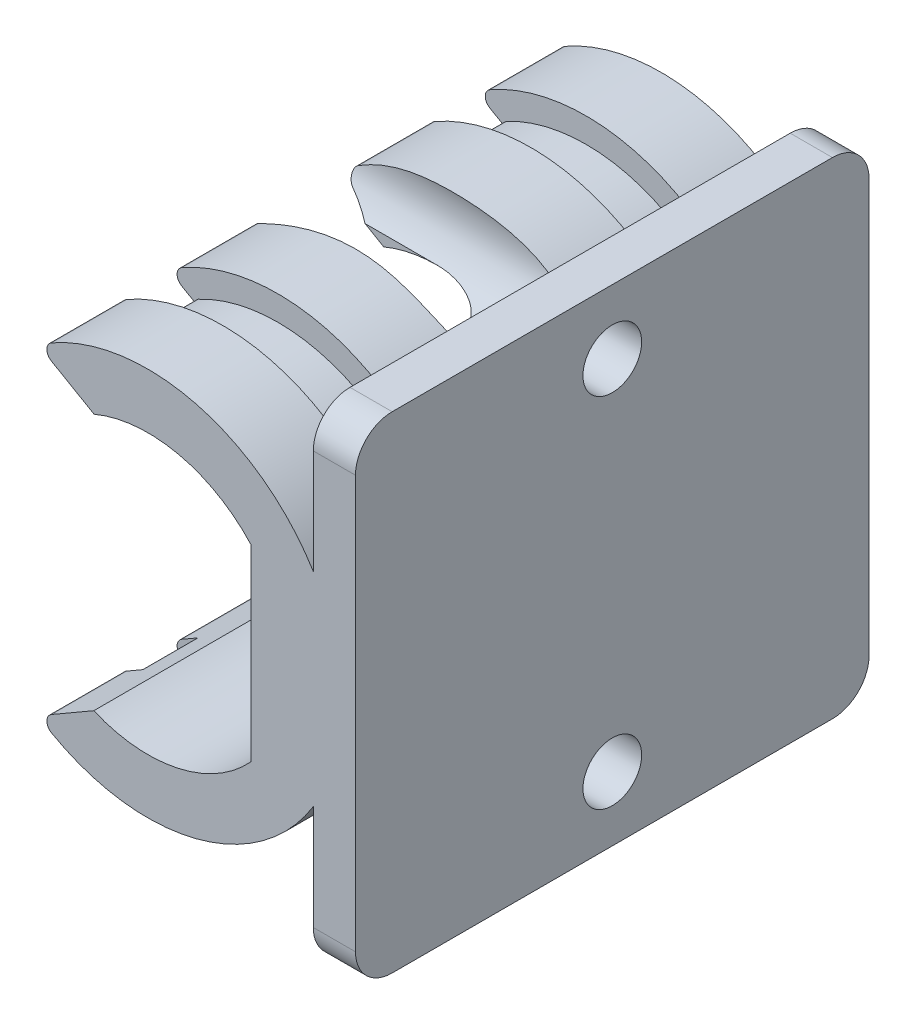
SolidWorks part; units mm, degrees
ref_plane "Alzado" through (0, 0, 0) normal (0, 0, 1) x (1, 0, 0)
ref_plane "Planta" through (0, 0, 0) normal (0, 1, 0) x (1, 0, 0)
ref_plane "Vista lateral" through (0, 0, 0) normal (1, 0, 0) x (0, 0, -1)
sketch "Croquis1" plane through (0, 0, 0) normal (0, 0, 1) x (1, 0, 0)
  line L0 (-9.8945, -9.6573) -> (-6.8675, -7.9093)
  line L1 (-9.8945, 7.8551) -> (-6.8511, 6.0976)
  arc A0 (-6.8675, -7.9093) -> (-6.8511, 6.0976) centre (-3.9083, -0.9093) ccw
  arc A1 (-9.8945, -9.6573) -> (-9.8945, 7.8551) centre (-3.9265, -0.9011) ccw
  point P0 (-6.8675, -7.9093)
  point P1 (-6.8675, 6.0907)
  point P2 (1.6915, 4.2287)
  point P3 (-1.2035, 9.3397)
  point P4 (6.6605, -1.3538)
  point P5 (-9.8945, -9.6573)
extrude "Saliente-Extruir1" add sketch "Croquis1" along normal blind 14.6 and the other way blind 14.6
sketch "Croquis2" plane through (0, 0, 14.6) normal (0, 0, 1) x (1, 0, 0)
  line L1 (1.6917, 4.2285) -> (1.6917, -6.0471)
  arc A0 (-6.8675, -7.9093) -> (-6.8511, 6.0976) centre (-3.9083, -0.9093) ccw construction
  arc A1 (1.6917, -6.0471) -> (1.6917, 4.2285) centre (-3.9083, -0.9093) ccw
  dimension "D1" = 5.6
extrude "Saliente-Extruir2" add sketch "Croquis2" against normal blind 2.6
mirror "Simetría1" about plane through (0, 0, 0) normal (0, 0, 1) of "Saliente-Extruir2"
sketch "Croquis3" plane through (0, 0, 0) normal (0, 0, 1) x (1, 0, 0)
  line L0 (1.6917, -0.9093) -> (20.3236, -0.9093) construction
  line L1 (1.6917, 4.2285) -> (1.6917, -6.0471) construction
  line L3 (5.1, 23.0597) -> (7.4, 23.0597)
  line L4 (5.1, 23.0597) -> (5.1, -24.8783)
  line L5 (5.1, -24.8783) -> (7.4, -24.8783)
  line L6 (7.4, 23.0597) -> (7.4, -24.8783)
  line L7 (5.1, 23.0597) -> (7.4, -24.8783) construction
  line L8 (5.1, -24.8783) -> (7.4, 23.0597) construction
  point P4 (6.25, -0.9093)
  dimension "D1" = 2.3
  dimension "D2" = 5.1
extrude "Saliente-Extruir3" add sketch "Croquis3" along normal up to surface (14.6 mm away) and the other way up to surface (14.6 mm away) up to face at (-2.1614, -0.9063, 14.6) other way up to face at (-2.1614, -0.9063, -14.6)
sketch "Croquis6" plane through (7.4, 0, 0) normal (1, 0, 0) x (0, 0, -1)
  line L0 (0, 23.0597) -> (0, -24.8783) construction
  line L1 (-14.6, 23.0597) -> (14.6, 23.0597) construction
  line L2 (-14.6, -24.8783) -> (14.6, -24.8783) construction
  line L3 (14.6, 4.2285) -> (14.6, -6.0471) construction
  line L4 (14.6, 4.2285) -> (14.6, -6.0471) construction
  line L5 (14.6, -0.9093) -> (-26.9521, -0.9093) construction
  circle A0 centre (0, 8.8407) radius 1.6
  circle A1 centre (0, -10.6593) radius 1.6
  dimension "D1" = 3.2
  dimension "D2" = 9.75
extrude "Cortar-Extruir1" cut sketch "Croquis6" against normal blind 20
sketch "Croquis7" plane through (5.1, 0, 0) normal (-1, 0, 0) x (0, 0, 1)
  circle A0 centre (0, -10.6593) radius 1.6 construction
  circle A1 centre (0, -10.6593) radius 1.6 construction
  circle A2 centre (0, -10.6593) radius 2.8
  circle A3 centre (0, 8.8407) radius 1.6 construction
  circle A4 centre (0, 8.8407) radius 1.6 construction
  circle A5 centre (0, 8.8407) radius 2.8
  dimension "D1" = 5.6
extrude "Cortar-Extruir2" cut sketch "Croquis7" along normal blind 20 contours A2
sketch "Croquis8" plane through (5.1, 0, 0) normal (-1, 0, 0) x (0, 0, 1)
  circle A0 centre (0, 8.8407) radius 1.6 construction
  circle A1 centre (0, 8.8407) radius 1.6 construction
  circle A2 centre (0, 8.8407) radius 2.8
  dimension "D1" = 5.6
extrude "Cortar-Extruir3" cut sketch "Croquis8" along normal blind 33
sketch "Croquis9" plane through (7.4, 0, 0) normal (1, 0, 0) x (0, 0, -1)
  line L0 (-12, 4.2285) -> (-12, -6.0471) construction
  line L2 (-14.6068, -0.9093) -> (14.6068, -0.9093) construction
  line L3 (-12, 4.2285) -> (-12, -6.0471) construction
  line L5 (-14, 12.3407) -> (14, 12.3407)
  line L6 (-14, 12.3407) -> (-14, -14.1593)
  line L7 (-14, -14.1593) -> (14, -14.1593)
  line L8 (14, 12.3407) -> (14, -14.1593)
  line L9 (-14, 12.3407) -> (14, -14.1593) construction
  line L10 (12, 4.2285) -> (12, -6.0471) construction
  line L11 (12, 4.2285) -> (12, -6.0471) construction
  line L12 (-14, -14.1593) -> (14, 12.3407) construction
  circle A0 centre (0, -10.6593) radius 1.6 construction
  circle A1 centre (0, -10.6593) radius 1.6 construction
  circle A2 centre (0, -10.6593) radius 2.5 construction
  circle A3 centre (0, 8.8407) radius 1.6 construction
  circle A4 centre (0, 8.8407) radius 1.6 construction
  point P0 (0, -0.9093)
  point P1 (0, -0.9093)
  point P13 (0, -13.1593)
  dimension "D1" = 5
  dimension "D2" = 3.5
  dimension "D3" = 29.2136
  dimension "D4" = 2
  dimension "D5" = 2
extrude "Cortar-Extruir4" cut sketch "Croquis9" against normal blind 33 flip side to cut
sketch "Croquis10" plane through (0, 0, 0) normal (0, 1, 0) x (1, 0, 0)
  line L0 (5.1, 6.9) -> (5.1, 9.9)
  line L1 (5.1, 14) -> (5.1, -14) construction
  line L2 (5.1, 14) -> (5.1, -14) construction
  line L3 (5.1, 0) -> (-22.1509, 0) construction
  line L4 (-9.8945, -14) -> (5.1, -14) construction
  line L5 (3.4, 1.5) -> (5.1, 1.5) construction
  line L6 (3.4, 1.5) -> (3.4, -1.5) construction
  line L7 (3.4, -1.5) -> (5.1, -1.5) construction
  line L8 (5.1, 1.5) -> (5.1, -1.5) construction
  line L9 (3.4, 1.5) -> (5.1, -1.5) construction
  line L10 (3.4, -1.5) -> (5.1, 1.5) construction
  line L11 (-16.6695, -2.8) -> (16.7616, -2.8) construction
  line L12 (-16.6695, 2.8) -> (16.7616, 2.8) construction
  line L13 (4.25, -2.8) -> (4.25, -14) construction
  line L14 (3.4, -6.9) -> (5.1, -6.9)
  line L15 (3.4, -6.9) -> (3.4, -9.9)
  line L16 (3.4, -9.9) -> (5.1, -9.9)
  line L17 (5.1, -6.9) -> (5.1, -9.9)
  line L18 (3.4, -6.9) -> (5.1, -9.9) construction
  line L19 (3.4, -9.9) -> (5.1, -6.9) construction
  line L20 (3.4, 9.9) -> (5.1, 9.9)
  line L21 (3.4, 6.9) -> (3.4, 9.9)
  line L22 (3.4, 6.9) -> (5.1, 6.9)
  spline S0 degree 3 poles (128.005, -1992.52) (-15.0747, -49.4602) (-25.3337, 1.339) (-8.7005, 2.7916) (-8.3855, 2.8007) (-7.7374, 2.7992) (-7.407, 2.7886) (-6.7413, 2.7605) (-6.0683, 2.7254) (-5.3803, 2.695) (-4.6844, 2.6733) (-4.3308, 2.6669) (-3.2809, 2.6652) (-2.5895, 2.6888) (-1.2225, 2.7532) (-0.5431, 2.7938) (0.4252, 2.8022) (0.741, 2.7961) (1.3584, 2.7504) (1.6617, 2.7102) (2.0921, 2.6101) (2.2319, 2.5701) (2.5039, 2.4731) (2.6367, 2.4159) (3.0167, 2.2152) (3.2455, 2.044) (3.5422, 1.7082) (3.631, 1.5857) (3.788, 1.3164) (3.8568, 1.1676) (3.9665, 0.8563) (4.0084, 0.6932) (4.0655, 0.3504) (4.0799, 0.1725) (4.0796, -0.1787) (4.0648, -0.3571) (4.007, -0.6995) (3.9646, -0.8637) (3.8522, -1.1787) (3.7841, -1.3243) (3.6256, -1.5937) (3.5345, -1.718) (3.3375, -1.9388) (3.2308, -2.0367) (3.002, -2.2115) (2.8794, -2.2884) (2.5, -2.4867) (2.2283, -2.5791) (1.651, -2.7121) (1.3501, -2.7513) (0.7346, -2.7963) (0.4185, -2.8023) (-0.2301, -2.7963) (-0.5635, -2.7843) (-1.233, -2.7545) (-1.5708, -2.7368) (-2.2524, -2.7047) (-2.5963, -2.6903) (-3.2904, -2.6708) (-3.6422, -2.6657) (-4.6971, -2.6678) (-5.3885, -2.6941) (-6.4093, -2.7432) (-6.7469, -2.7608) (-7.4167, -2.789) (-7.7476, -2.7994) (-8.3898, -2.8005) (-8.7027, -2.7914) (-25.097, -1.3576) (-17.6157, 48.092) (106.0424, 1993.882) knots -1.637998 -1.637998 -1.637998 -1.637998 0.03125 0.03125 0.0625 0.0625 0.09375 0.09375 0.125 0.15625 0.15625 0.1875 0.1875 0.25 0.25 0.3125 0.3125 0.34375 0.34375 0.375 0.375 0.390625 0.390625 0.40625 0.40625 0.4375 0.4375 0.453125 0.453125 0.46875 0.46875 0.484375 0.484375 0.5 0.5 0.515625 0.515625 0.53125 0.53125 0.546875 0.546875 0.5625 0.5625 0.578125 0.578125 0.59375 0.59375 0.625 0.625 0.65625 0.65625 0.6875 0.6875 0.71875 0.71875 0.75 0.75 0.78125 0.78125 0.8125 0.8125 0.875 0.875 0.90625 0.90625 0.9375 0.9375 0.96875 0.96875 2.620269 2.620269 2.620269 2.620269 only from (-9.8945, 2.6208) to (-9.8945, -2.6208) construction
  spline S1 degree 3 poles (-9.8945, 2.6208) (-9.6082, 2.6942) (-9.3118, 2.7382) (-8.7005, 2.7916) (-8.3855, 2.8007) (-7.7374, 2.7992) (-7.407, 2.7886) (-6.7413, 2.7605) (-6.0683, 2.7254) (-5.3803, 2.695) (-4.6844, 2.6733) (-4.3308, 2.6669) (-3.2809, 2.6652) (-2.5895, 2.6888) (-1.2225, 2.7532) (-0.5431, 2.7938) (0.4252, 2.8022) (0.741, 2.7961) (1.3584, 2.7504) (1.6617, 2.7102) (2.0921, 2.6101) (2.2319, 2.5701) (2.5039, 2.4731) (2.6367, 2.4159) (3.0167, 2.2152) (3.2455, 2.044) (3.5422, 1.7082) (3.631, 1.5857) (3.788, 1.3164) (3.8568, 1.1676) (3.9665, 0.8563) (4.0084, 0.6932) (4.0655, 0.3504) (4.0799, 0.1725) (4.0796, -0.1787) (4.0648, -0.3571) (4.007, -0.6995) (3.9646, -0.8637) (3.8522, -1.1787) (3.7841, -1.3243) (3.6256, -1.5937) (3.5345, -1.718) (3.3375, -1.9388) (3.2308, -2.0367) (3.002, -2.2115) (2.8794, -2.2884) (2.5, -2.4867) (2.2283, -2.5791) (1.651, -2.7121) (1.3501, -2.7513) (0.7346, -2.7963) (0.4185, -2.8023) (-0.2301, -2.7963) (-0.5635, -2.7843) (-1.233, -2.7545) (-1.5708, -2.7368) (-2.2524, -2.7047) (-2.5963, -2.6903) (-3.2904, -2.6708) (-3.6422, -2.6657) (-4.6971, -2.6678) (-5.3885, -2.6941) (-6.4093, -2.7432) (-6.7469, -2.7608) (-7.4167, -2.789) (-7.7476, -2.7994) (-8.3898, -2.8005) (-8.7027, -2.7914) (-9.3116, -2.7382) (-9.6076, -2.6943) (-9.8945, -2.6208) knots 0 0 0 0 0.03125 0.03125 0.0625 0.0625 0.09375 0.09375 0.125 0.15625 0.15625 0.1875 0.1875 0.25 0.25 0.3125 0.3125 0.34375 0.34375 0.375 0.375 0.390625 0.390625 0.40625 0.40625 0.4375 0.4375 0.453125 0.453125 0.46875 0.46875 0.484375 0.484375 0.5 0.5 0.515625 0.515625 0.53125 0.53125 0.546875 0.546875 0.5625 0.5625 0.578125 0.578125 0.59375 0.59375 0.625 0.625 0.65625 0.65625 0.6875 0.6875 0.71875 0.71875 0.75 0.75 0.78125 0.78125 0.8125 0.8125 0.875 0.875 0.90625 0.90625 0.9375 0.9375 0.96875 0.96875 1 1 1 1 construction
  point P4 (4.25, 0)
  point P10 (4.25, -8.4)
  dimension "D1" = 1.7
  dimension "D2" = 3
  dimension "D3" = 3
  dimension "D4" = 1.7
extrude "Cortar-Extruir5" cut sketch "Croquis10" along normal through all and the other way through all
sketch "Croquis11" plane through (0, 0, 0) normal (0, 1, 0) x (1, 0, 0)
  line L0 (-12.5185, 1.7936) -> (-3.9112, 1.7936)
  line L1 (-12.4395, -1.7907) -> (-3.9112, -1.7935)
  line L2 (-3.9112, 1.7936) -> (-3.9112, -1.7935)
  line L3 (-12.5185, 1.7936) -> (-12.4395, -1.7907)
  point P6 (-3.9112, 1.7936)
  point P7 (-3.9112, -1.7935)
extrude "Cortar-Extruir6" cut sketch "Croquis11" against normal through all and the other way through all contours L3 L1 L2 L0
fillet "Redondeo1" radius 2 4 edges at (6.25, 12.3407, -14) (6.25, -14.1593, -14) (6.25, 12.3407, 14) (6.25, -14.1593, 14)
fillet "Redondeo3" radius 0.5 4 edges at (-9.8945, -9.6573, 8.3073) (-9.8945, -9.6573, -8.3073) (-9.8945, 7.8551, -8.3104) (-9.8945, 7.8551, 8.3104)
ref_plane "Plano1" through (3.4, 6.7547, 9.9) normal (0.7225, -0.6914, 0) x (0, 0, -1)
sketch "Croquis12" plane through (3.4, 6.7547, 9.9) normal (0.7225, -0.6914, 0) x (0, 0, -1)
  line L0 (0, 0) -> (3, 0) construction
  line L1 (0, 0) -> (3, 0) construction
  line L2 (3, 0) -> (3, -4.031) construction
  line L3 (0, 0.01) -> (3, 0.01)
  line L4 (0, 0.01) -> (0, -1.5)
  line L5 (0, -1.5) -> (3, -1.5)
  line L6 (3, 0.01) -> (3, -1.5)
  dimension "D1" = 1.51
sketch "Croquis13" plane through (0, 0, 14) normal (0, 0, 1) x (1, 0, 0)
  arc A0 (-9.1714, -10.1086) -> (5.1, -6.4519) centre (-3.9265, -0.9011) ccw construction
  arc A1 (-9.1714, -10.1086) -> (5.1, -6.4519) centre (-3.9265, -0.9011) ccw construction
  arc A2 (5.1, 4.6497) -> (5.1, -6.4519) centre (-3.9265, -0.9011) ccw
ref_plane "Plano2" through (0.3394, -0.3248, 0) normal (0.7225, -0.6914, 0) x (0, 0, -1)
sketch "Croquis15" plane through (0.3394, -0.3248, 0) normal (0.7225, -0.6914, 0) x (0, 0, -1)
  line L0 (-9.9, 6.8854) -> (-9.9, 7.2309) construction
  line L1 (-9.9, 6.9867) -> (-6.9, 6.9867)
  line L2 (-9.9, 6.9867) -> (-9.9, 5.4867)
  line L3 (-9.9, 5.4867) -> (-6.9, 5.4867)
  line L4 (-6.9, 6.9867) -> (-6.9, 5.4867)
  line L5 (-9.9, 7.2309) -> (-9.9, 3.1998) construction
  line L6 (-6.9, 7.2309) -> (-6.9, 3.1998) construction
  dimension "D1" = 1.5
sweep "Cortar-Barrer2" cut profiles "Croquis15" path "Croquis13"
mirror "Simetría3" about plane through (0, 0, 0) normal (0, 0, 1) of "Cortar-Barrer2"
sketch "Croquis16" plane through (5.1, 0, 0) normal (-1, 0, 0) x (0, 0, 1)
  line L1 (-6.9, 4.8346) -> (-6.9, 4.6497)
  line L2 (-6.9, 4.6497) -> (-9.9, 4.6497)
  line L3 (-9.9, 4.6497) -> (-9.9, 4.8346)
  line L4 (-9.9, 4.8346) -> (-6.9, 4.8346)
  line L5 (0, 0) -> (0, 16.7386) construction
  line L6 (9.9, 4.8346) -> (6.9, 4.8346)
  line L7 (9.9, 4.6497) -> (9.9, 4.8346)
  line L8 (6.9, 4.6497) -> (9.9, 4.6497)
  line L9 (6.9, 4.8346) -> (6.9, 4.6497)
  line L10 (-14, -12.1593) -> (-14, 10.3407) construction
  line L11 (-14, -12.1593) -> (-14, 10.3407) construction
  line L12 (-14, -0.9093) -> (34.9508, -0.9093) construction
extrude "Saliente-Extruir4" add sketch "Croquis16" against normal up to next
sketch "Croquis17" plane through (5.1, 0, 0) normal (-1, 0, 0) x (0, 0, 1)
  line L1 (-9.9, -6.4519) -> (-6.9, -6.4519)
  line L2 (-9.9, -6.4519) -> (-9.9, -6.6368)
  line L3 (-9.9, -6.6368) -> (-6.9, -6.6368)
  line L4 (-6.9, -6.4519) -> (-6.9, -6.6368)
  line L5 (6.9, -6.4519) -> (9.9, -6.4519)
  line L6 (6.9, -6.4519) -> (6.9, -6.6368)
  line L7 (6.9, -6.6368) -> (9.9, -6.6368)
  line L8 (9.9, -6.4519) -> (9.9, -6.6368)
extrude "Saliente-Extruir5" add sketch "Croquis17" against normal up to next
fillet "Redondeo6" radius 0.2 4 edges at (-8.5778, -8.8969, -8.4) (-8.5778, -8.8969, 8.4) (-8.5778, 7.0947, -8.4) (-8.5778, 7.0947, 8.4)
fillet "Redondeo7" radius 0.5 4 edges at (3.4, -6.5483, 8.4) (3.4, -6.5483, -8.4) (3.4, 4.7461, -8.4) (3.4, 4.7461, 8.4)
